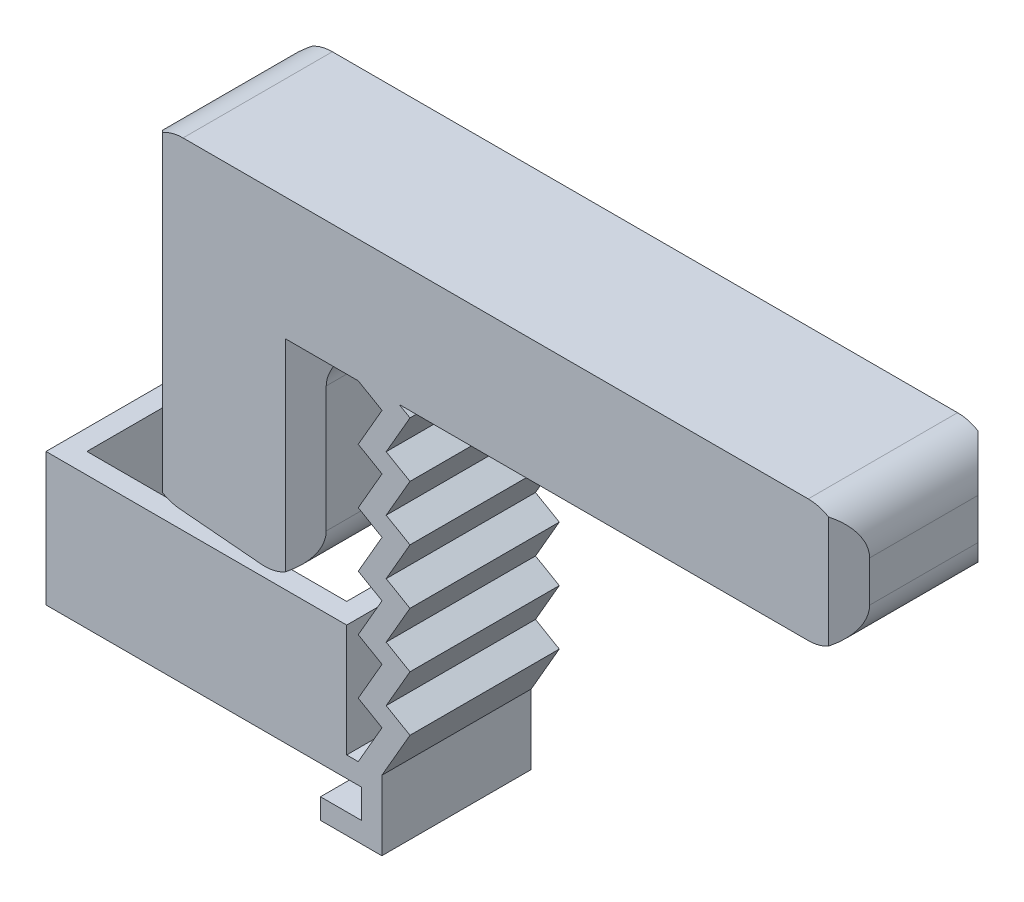
SolidWorks part; units mm, degrees
ref_plane "Front Plane" through (0, 0, 0) normal (0, 0, 1) x (1, 0, 0)
ref_plane "Top Plane" through (0, 0, 0) normal (0, 1, 0) x (1, 0, 0)
ref_plane "Right Plane" through (0, 0, 0) normal (1, 0, 0) x (0, 0, -1)
sketch "Sketch2" plane through (0, 0, 0) normal (0, 1, 0) x (1, 0, 0)
  line L0 (30.215, 56.2321) -> (30.215, 50.4321) construction
  line L1 (30.215, 50.4321) -> (17.515, 50.4321) construction
  line L2 (17.515, 50.4321) -> (17.515, 56.2321) construction
  line L3 (30.215, 56.2321) -> (30.215, 50.4321)
  line L4 (30.215, 50.4321) -> (17.515, 50.4321)
  line L5 (17.515, 50.4321) -> (17.515, 56.2321)
  line L6 (31.215, 56.7321) -> (31.215, 49.4321)
  line L7 (31.215, 49.4321) -> (16.515, 49.4321)
  line L8 (16.515, 49.4321) -> (16.515, 56.7321)
  line L12 (28.215, 56.7321) -> (31.215, 56.7321)
  line L14 (31.215, 56.2321) -> (31.215, 49.4321) construction
  line L15 (16.515, 49.4321) -> (16.515, 56.2321) construction
  line L18 (30.215, 56.2321) -> (28.215, 56.2321)
  line L19 (28.215, 56.2321) -> (28.215, 56.7321)
  line L20 (16.515, 56.7321) -> (19.515, 56.7321)
  line L21 (19.515, 56.7321) -> (19.515, 56.2321)
  line L22 (17.515, 56.2321) -> (30.215, 56.2321) construction
  line L23 (19.515, 56.2321) -> (17.515, 56.2321)
  point P2 (19.515, 56.4899)
  dimension "D2" = 2
  dimension "D3" = 0.5
  dimension "D1" = 1
extrude "Boss-Extrude3" add sketch "Sketch2" along normal blind 6.5 contours L6 L7 L8 L20 L21 L23 L5 L4 L3 L18 L19 L12
sketch "Sketch1" plane through (-49.4321, 0, -49.4321) normal (0, 0, 1) x (1, 0, 0)
  line L27 (81.2124, 1) -> (82.3761, 3.0155)
  line L28 (82.3761, 3.0155) -> (81.2124, 3.6874)
  line L31 (79.3671, -1.41) -> (81.3671, -1.41)
  line L32 (81.3671, -1.41) -> (81.3671, 0)
  line L33 (81.3671, 0) -> (80.6471, 0)
  line L34 (81.3671, 0) -> (61.0471, 0) construction
  line L35 (81.2124, 14.437) -> (82.3761, 16.4525)
  line L36 (81.3671, -1.51) -> (81.3671, 0) construction
  line L37 (79.3671, -2.41) -> (82.3671, -2.41)
  line L38 (82.3671, -2.41) -> (82.3671, 1)
  line L39 (81.2124, 1) -> (80.6471, 1)
  line L40 (79.3671, -1.41) -> (79.3671, -2.41)
  line L41 (80.6471, 1) -> (80.6471, 0)
  line L42 (81.2124, 3.6874) -> (82.3761, 5.7029)
  line L43 (82.3761, 5.7029) -> (81.2124, 6.3748)
  line L44 (81.2124, 6.3748) -> (82.3761, 8.3903)
  line L45 (82.3761, 8.3903) -> (81.2124, 9.0622)
  line L46 (81.2124, 9.0622) -> (82.3761, 11.0777)
  line L47 (82.3761, 11.0777) -> (81.2124, 11.7496)
  line L48 (81.2124, 11.7496) -> (82.3761, 13.7651)
  line L49 (82.3761, 13.7651) -> (81.2124, 14.437)
  line L50 (82.3671, 1) -> (83.7421, 3.3816)
  line L51 (104.7846, 22.9706) -> (104.7846, 16.9706) construction
  line L52 (82.5784, 4.0534) -> (83.7421, 6.069)
  line L53 (83.7421, 6.069) -> (82.5784, 6.7408)
  line L54 (82.5784, 6.7408) -> (83.7421, 8.7564)
  line L55 (83.7421, 8.7564) -> (82.5784, 9.4282)
  line L56 (82.5784, 9.4282) -> (83.7421, 11.4437)
  line L57 (83.7421, 11.4437) -> (82.5784, 12.1156)
  line L58 (82.5784, 12.1156) -> (83.7421, 14.1311)
  line L59 (105.2124, 17.1244) -> (83.2124, 17.1244)
  line L60 (82.1277, 0.5854) -> (83.7421, 3.3816) construction
  line L61 (82.3761, 16.4525) -> (81.2124, 17.1244)
  line L62 (83.7421, 3.3816) -> (82.5784, 4.0534)
  line L63 (82.5784, 4.0534) -> (83.7421, 6.069)
  line L64 (83.7421, 14.1311) -> (81.7124, 15.303) construction
  line L65 (83.7421, 6.069) -> (82.5784, 6.7408)
  line L66 (82.5784, 6.7408) -> (83.7421, 8.7564)
  line L67 (83.7421, 8.7564) -> (82.5784, 9.4282)
  line L68 (82.5784, 9.4282) -> (83.7421, 11.4437)
  line L69 (83.7421, 11.4437) -> (82.5784, 12.1156)
  line L70 (82.5784, 12.1156) -> (83.7421, 14.1311)
  line L71 (83.7421, 14.1311) -> (82.5784, 14.803)
  line L72 (82.5784, 14.803) -> (83.7421, 16.8185)
  line L73 (83.7421, 16.8185) -> (83.2124, 17.1244)
  line L74 (83.7421, 16.8185) -> (81.7124, 17.9904) construction
  line L75 (81.2617, 1.0854) -> (82.3761, 3.0155) construction
  line L76 (82.3671, 1) -> (80.6471, 1) construction
  line L77 (82.1277, 0.5854) -> (83.7421, 3.3816) construction
  line L78 (78.6471, 17.1244) -> (78.6471, 6.8)
  line L79 (78.6471, 6.8) -> (70.6471, 7.4999)
  line L80 (70.6471, 7.4999) -> (70.6471, 23.1244)
  line L81 (70.6471, 23.1244) -> (105.2124, 23.1244)
  line L82 (105.2124, 23.1244) -> (105.2124, 17.1244)
  line L83 (81.2124, 17.1244) -> (78.6471, 17.1244)
  line L85 (82.3671, -2.41) -> (82.3671, 1) construction
  line L86 (83.7421, 3.3816) -> (82.5784, 4.0534) construction
  point P12 (80.9409, 1)
  point P61 (106.3093, 22.9706)
  point P63 (105.3066, 16.9706)
  point P66 (105.0157, 16.9706)
  point P69 (0, 0)
  point P70 (0, 0)
  point P71 (82.3671, 1.8983)
  point P72 (82.3671, 1.0578)
  point P73 (104.2124, 16.9706)
  line M42 (80.6471, 0) -> (80.6471, 6.5)
  dimension "D3" = 0.1
  dimension "D4" = 2
  dimension "D6" = 30
  dimension "D7" = 90
  dimension "D9" = 2.75
  dimension "D11" = 85
  dimension "D12" = 1
  dimension "D13" = 8
  dimension "D14" = 0.3
  dimension "D15" = 6
  dimension "D16" = 22
  dimension "D17" = 28.1576
  dimension "D18" = 2.52
  dimension "D2" = 1
  dimension "D5" = 1
  dimension "D8" = 1
  dimension "D1" = 6
extrude "Boss-Extrude4" add sketch "Sketch1" against normal up to surface (7.3 mm away) contours L27 L39 L33 L32 L31 L40 L37 L38 L50 L62 L52 L53 L54 L55 L56 L57 L58 L71 L72 L73 L59 L82 L81 L80 L79 L78 L83 L61 L35 L49 L48 L47 L46 L45 L44 L43 L42 L28 M42 region at (32.7343, 1.7929, -49.4321) up to face at (29.715, 3.25, -56.7321)
chamfer "Chamfer1" distance 1 angle 45 6 edges at (21.215, 15.3121, -49.4321) (29.215, 11.9622, -49.4321) (29.215, 11.9622, -56.7321) (21.215, 15.3121, -56.7321) (55.7803, 20.1244, -49.4321) (55.7803, 20.1244, -56.7321)
fillet "Fillet1" radius 2 6 edges at (29.215, 6.8, -53.0821) (29.215, 17.1244, -53.0821) (21.215, 7.4999, -53.0821) (21.215, 23.1244, -53.0821) (55.7803, 17.1244, -53.0821) (55.7803, 23.1244, -53.0821)
